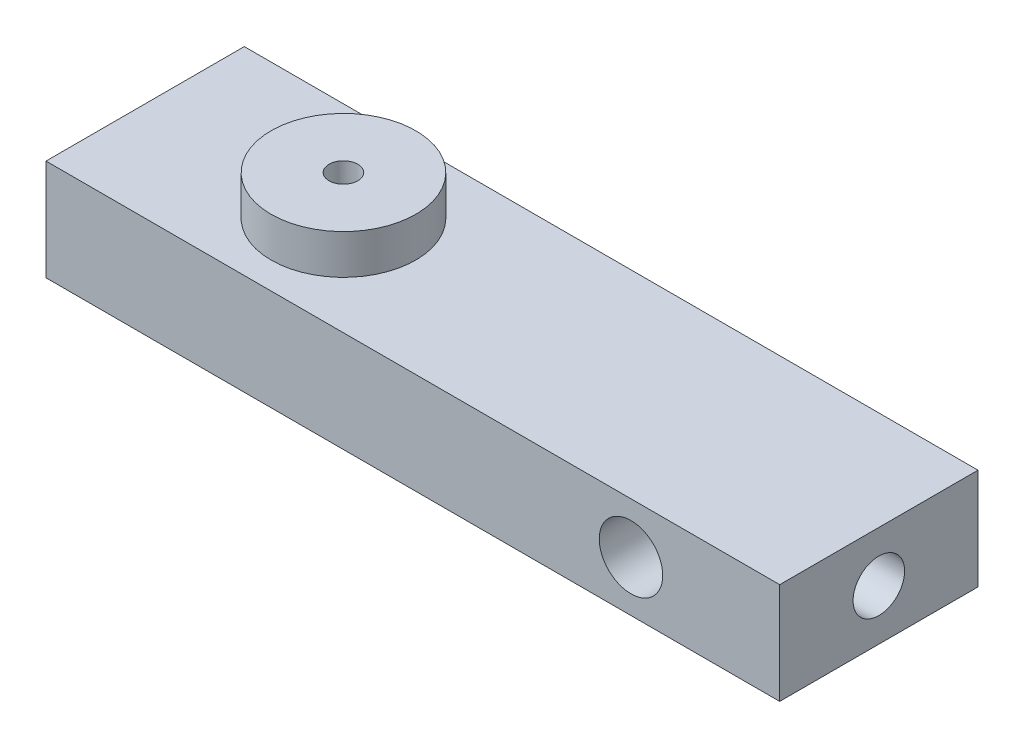
SolidWorks part; units mm, degrees
material "ABS"
ref_plane "前视基准面" through (0, 0, 0) normal (0, 0, 1) x (1, 0, 0)
ref_plane "上视基准面" through (0, 0, 0) normal (0, 1, 0) x (1, 0, 0)
ref_plane "右视基准面" through (0, 0, 0) normal (1, 0, 0) x (0, 0, -1)
other "Configuration Table"
sketch "草图1" plane through (0, 0, 0) normal (0, 1, 0) x (1, 0, 0)
  line L1 (-7.5, 5) -> (7.5, 5)
  line L2 (-7.5, 5) -> (-7.5, -5)
  line L3 (-7.5, -5) -> (7.5, -5)
  line L4 (7.5, 5) -> (7.5, -5)
  line L5 (-7.5, 5) -> (7.5, -5) construction
  line L6 (-7.5, -5) -> (7.5, 5) construction
  point P0 (0, 0)
  dimension "D1" = 15
  dimension "D2" = 10
extrude "凸台-拉伸1" add sketch "草图1" along normal blind 5.1
sketch "草图2" plane through (0, 0, 5) normal (0, 0, 1) x (1, 0, 0)
  circle A0 centre (0, 2.55) radius 1.6
  dimension "D1" = 3.2
  dimension "D2" = 2.55
extrude "切除-拉伸1" cut sketch "草图2" against normal through all
sketch "草图3" plane through (7.5, 0, 0) normal (1, 0, 0) x (0, 0, -1)
  line L3 (-2.5032, 2.55) -> (3.0272, 2.55) construction
  line L4 (-5, 5.1) -> (5, 5.1) construction
  line L5 (-5, 0) -> (5, 0) construction
  circle A0 centre (0, 2.55) radius 1.3
  dimension "D1" = 2.6
extrude "切除-拉伸2" cut sketch "草图3" against normal blind 3.8
sketch "草图4" plane through (3.7, 0, 0) normal (1, 0, 0) x (0, 0, -1)
  circle A0 centre (0, 2.55) radius 0.575
  dimension "D1" = 1.15
extrude "切除-拉伸3" cut sketch "草图4" against normal up to next
sketch "草图5" plane through (-7.5, 0, 0) normal (-1, 0, 0) x (0, 0, 1)
  line L4 (-5, 0) -> (5, 0)
  line L5 (5, 0) -> (5, 5.1)
  line L6 (5, 5.1) -> (-5, 5.1)
  line L7 (-5, 5.1) -> (-5, 0)
  line L8 (-5, 0) -> (5, 0)
  line L9 (5, 0) -> (5, 5.1)
  line L10 (5, 5.1) -> (-5, 5.1)
  line L11 (-5, 5.1) -> (-5, 0)
  dimension "D1" = 0
extrude "凸台-拉伸2" add sketch "草图5" along normal blind 22
sketch "草图6" plane through (0, 5.1, 0) normal (0, 1, 0) x (1, 0, 0)
  line L0 (-29.5, -5) -> (-29.5, 5) construction
  circle A0 centre (-19.5, 0) radius 3.65
  dimension "D2" = 7.3
  dimension "D1" = 10
extrude "凸台-拉伸3" add sketch "草图6" along normal blind 2
sketch "草图7" plane through (0, 7.1, 0) normal (0, 1, 0) x (1, 0, 0)
  circle A0 centre (-19.5, 0) radius 0.725
  circle A1 centre (-19.5, 0) radius 3.65 construction
  dimension "D1" = 1.45
extrude "切除-拉伸4" cut sketch "草图7" against normal through all
